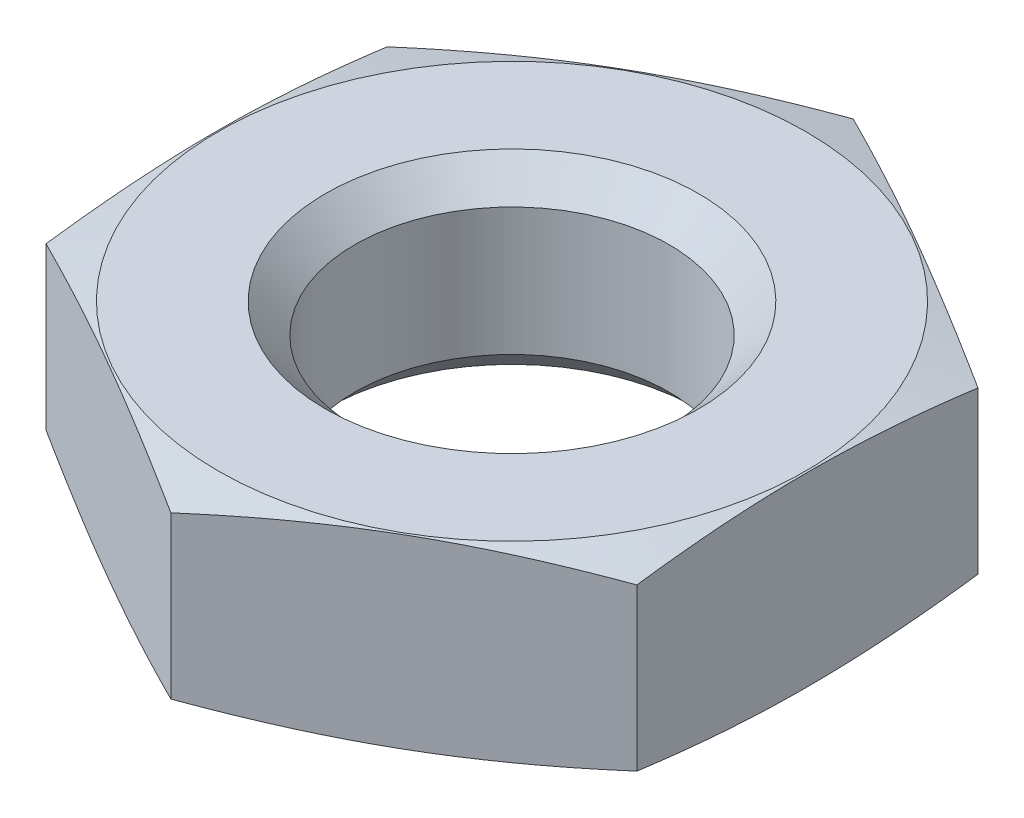
SolidWorks part; units mm, degrees
ref_plane "Front Plane" through (0, 0, 0) normal (0, 0, 1) x (1, 0, 0)
ref_plane "Top Plane" through (0, 0, 0) normal (0, 1, 0) x (1, 0, 0)
ref_plane "Right Plane" through (0, 0, 0) normal (1, 0, 0) x (0, 0, -1)
ref_plane "Plane1" through (0, 0, 0) normal (0, 0, 1) x (1, 0, 0)
sketch "Sketch1" plane through (0, 0, 0) normal (0, 0, 1) x (1, 0, 0)
  line L0 (0, 0) -> (9.45, 0)
  line L1 (9.45, 0) -> (20.6462, -3)
  line L2 (20.6462, -3) -> (9.45, -6)
  line L3 (9.45, -6) -> (0, -6)
  line L4 (0, -6) -> (0, 0)
  line L5 (0, -6) -> (0, 0) construction
revolve "Revolve1" add sketch "Sketch1" angle 360 about L5
ref_plane "Plane2" through (0, 0, 0) normal (0, 1, 0) x (1, 0, 0)
sketch "Sketch2" plane through (0, 0, 0) normal (0, 1, 0) x (1, 0, 0)
  line L0 (-38, 38) -> (-38, -38)
  line L1 (-38, -38) -> (38, -38)
  line L2 (38, -38) -> (38, 38)
  line L3 (38, 38) -> (-38, 38)
  line L4 (-9.5, -5.4848) -> (0, -10.9697)
  line L5 (0, -10.9697) -> (9.5, -5.4848)
  line L6 (9.5, -5.4848) -> (9.5, 5.4848)
  line L7 (9.5, 5.4848) -> (0, 10.9697)
  line L8 (0, 10.9697) -> (-9.5, 5.4848)
  line L9 (-9.5, 5.4848) -> (-9.5, -5.4848)
extrude "Cut-Extrude1" cut sketch "Sketch2" against normal blind 7 and the other way blind 7
ref_plane "Plane3" through (0, 0, 0) normal (0, 0, 1) x (1, 0, 0)
sketch "Sketch3" plane through (0, 0, 0) normal (0, 0, 1) x (1, 0, 0)
  line L0 (0, 0) -> (6, 0)
  line L1 (6, 0) -> (5.053, -0.947)
  line L2 (5.053, -0.947) -> (5.053, -5.053)
  line L3 (5.053, -5.053) -> (6, -6)
  line L4 (6, -6) -> (0, -6)
  line L5 (0, -6) -> (0, 0)
  line L6 (0, -6) -> (0, 0) construction
revolve "Cut-Revolve1" cut sketch "Sketch3" angle 360 about L6 reverse direction yes
cosmetic thread "Cosmetic Thread1" parameters "D1"=6, "D2"=12
